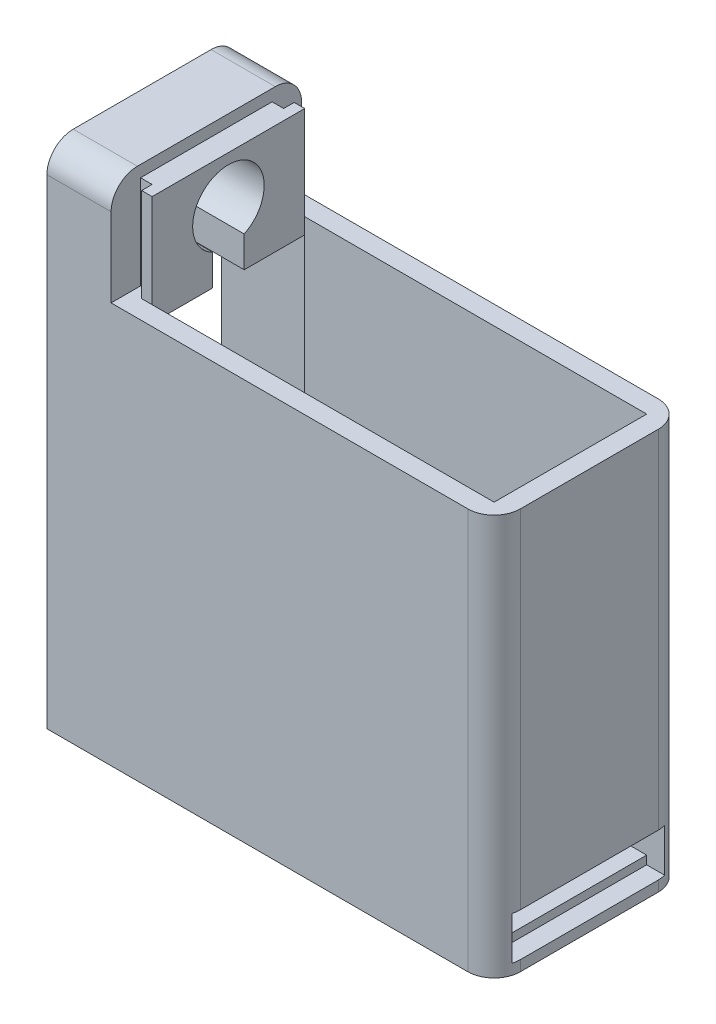
SolidWorks part; units mm, degrees
ref_plane "前视基准面" through (0, 0, 0) normal (0, 0, 1) x (1, 0, 0)
ref_plane "上视基准面" through (0, 0, 0) normal (0, 1, 0) x (1, 0, 0)
ref_plane "右视基准面" through (0, 0, 0) normal (1, 0, 0) x (0, 0, -1)
other "Configuration Table"
sketch "草图1" plane through (0, 0, 0) normal (0, 1, 0) x (1, 0, 0)
  line L1 (0, 29) -> (65, 29)
  line L2 (0, 29) -> (0, 0)
  line L3 (0, 0) -> (65, 0)
  line L4 (65, 29) -> (65, 0)
  dimension "D1" = 65
  dimension "D2" = 29
sketch "草图2" plane through (0, 0, 0) normal (0, 1, 0) x (1, 0, 0)
  line L0 (-3.6, 32.6) -> (68.6, 32.6)
  line L1 (-3.6, 32.6) -> (-3.6, -3.6)
  line L2 (-3.6, -3.6) -> (68.6, -3.6)
  line L3 (68.6, 32.6) -> (68.6, -3.6)
  dimension "D1" = 72.2
  dimension "D2" = 36.2
extrude "拉伸-薄壁1" add sketch "草图1" along normal blind 74.2 thin thin type one direction wall 3.6
extrude "凸台-拉伸2" add sketch "草图2" against normal blind 2
sketch "草图3" plane through (0, 0, 0) normal (1, 0, 0) x (0, 0, -1)
  line L1 (-0.6, 71.2) -> (29.6, 71.2)
  line L2 (-0.6, 71.2) -> (-0.6, 1)
  line L3 (-0.6, 1) -> (29.6, 1)
  line L4 (29.6, 71.2) -> (29.6, 1)
  dimension "D1" = 30.2
  dimension "D2" = 70.2
extrude "拉伸-薄壁2" add sketch "草图3" against normal blind 16.4 thin thin type one direction wall 3
sketch "草图4" plane through (0, 0, 0) normal (1, 0, 0) x (0, 0, -1)
  line L0 (-0.6, 71.2) -> (29.6, 71.2)
  line L1 (-0.6, 71.2) -> (-0.6, 1)
  line L2 (-0.6, 1) -> (29.6, 1)
  line L3 (29.6, 71.2) -> (29.6, 1)
  dimension "D1" = 30.2
  dimension "D2" = 70.2
extrude "切除-拉伸1" cut sketch "草图4" against normal blind 16.4
sketch "草图5" plane through (68.6, 0, 0) normal (1, 0, 0) x (0, 0, -1)
  line L1 (0, 0) -> (29, 0)
  line L2 (0, 0) -> (0, 4.8)
  line L3 (0, 4.8) -> (29, 4.8)
  line L4 (29, 0) -> (29, 4.8)
  dimension "D1" = 29
  dimension "D2" = 4.8
extrude "切除-拉伸2" cut sketch "草图5" against normal blind 5
sketch "草图8" plane through (-16.4, 0, 0) normal (-1, 0, 0) x (0, 0, 1)
  line L1 (-32.6, 74.2) -> (3.6, 74.2)
  line L2 (-32.6, 74.2) -> (-32.6, 94.2)
  line L3 (-32.6, 94.2) -> (3.6, 94.2)
  line L4 (3.6, 74.2) -> (3.6, 94.2)
  dimension "D1" = 20
extrude "凸台-拉伸3" add sketch "草图8" against normal blind 16.4
sketch "草图7" plane through (0, 0, 0) normal (1, 0, 0) x (0, 0, -1)
  line L1 (11.5, 88.2) -> (17.5, 88.2)
  line L2 (11.5, 88.2) -> (11.5, 71.2)
  line L3 (11.5, 71.2) -> (17.5, 71.2)
  line L4 (17.5, 88.2) -> (17.5, 71.2)
  line L5 (29, 71.2) -> (0, 71.2) construction
  dimension "D1" = 6
extrude "切除-拉伸3" cut sketch "草图7" against normal blind 17
sketch "草图9" plane through (-16.4, 0, 0) normal (-1, 0, 0) x (0, 0, 1)
  line L1 (-17.5, 71.2) -> (-11.5, 71.2)
  line L2 (-17.5, 71.2) -> (-17.5, 88.2)
  line L3 (-17.5, 88.2) -> (-11.5, 88.2)
  line L4 (-11.5, 71.2) -> (-11.5, 88.2)
extrude "凸台-拉伸4" add sketch "草图9" against normal blind 2
sketch "草图10" plane through (-16.4, 0, 0) normal (-1, 0, 0) x (0, 0, 1)
  circle A0 centre (-14.5, 83.2) radius 7.1
  dimension "D1" = 14.2
extrude "切除-拉伸4" cut sketch "草图10" against normal blind 3
sketch "草图11" plane through (0, 0, 3.6) normal (0, 0, 1) x (1, 0, 0)
  line L1 (-4.2, 94.2) -> (-2, 94.2)
  line L2 (-4.2, 94.2) -> (-4.2, 74.2)
  line L3 (-4.2, 74.2) -> (-2, 74.2)
  line L4 (-2, 94.2) -> (-2, 74.2)
extrude "切除-拉伸5" cut sketch "草图11" against normal blind 5.6
sketch "草图12" plane through (0, 0, -32.6) normal (0, 0, -1) x (-1, 0, 0)
  line L1 (2, 74.2) -> (4.2, 74.2)
  line L2 (2, 74.2) -> (2, 94.2)
  line L3 (2, 94.2) -> (4.2, 94.2)
  line L4 (4.2, 74.2) -> (4.2, 94.2)
extrude "切除-拉伸6" cut sketch "草图12" against normal blind 5.6
sketch "草图13" plane through (0, 94.2, 0) normal (0, 1, 0) x (1, 0, 0)
  line L1 (-2, 32.6) -> (0, 32.6)
  line L2 (-2, 32.6) -> (-2, 29)
  line L3 (-2, 29) -> (0, 29)
  line L4 (0, 32.6) -> (0, 29)
  line L5 (-2, -3.6) -> (0, -3.6)
  line L6 (-2, -3.6) -> (-2, 0)
  line L7 (-2, 0) -> (0, 0)
  line L8 (0, -3.6) -> (0, 0)
extrude "切除-拉伸7" cut sketch "草图13" against normal blind 20
fillet "圆角1" radius 5 1 edges at (-10.3, 94.2, 3.6)
fillet "圆角2" radius 5 1 edges at (-10.3, 94.2, -32.6)
fillet "圆角3" radius 5 2 edges at (68.6, 2.4, 0) (68.6, 36.1, 3.6)
fillet "圆角4" radius 5 2 edges at (68.6, 2.4, -29) (68.6, 36.1, -32.6)
sketch "草图14" plane through (0, 94.2, 0) normal (0, 1, 0) x (1, 0, 0)
  line L0 (-4.2, 2) -> (-4.2, -3.6) construction
  line L1 (0, 29) -> (-4.2, 29)
  line L2 (0, 29) -> (0, 0)
  line L3 (0, 0) -> (-4.2, 0)
  line L4 (-4.2, 29) -> (-4.2, 0)
extrude "切除-拉伸8" cut sketch "草图14" against normal blind 2.2
sketch "草图15" plane through (-13.4, 0, 0) normal (-1, 0, 0) x (0, 0, 1)
  circle A0 centre (-14.5, 83.2) radius 6.8
extrude "切除-拉伸9" cut sketch "草图15" against normal blind 20
sketch "草图16" plane through (-14.4, 0, 0) normal (1, 0, 0) x (0, 0, -1)
  line L1 (17.5, 71.2) -> (11.5, 71.2)
  line L2 (17.5, 71.2) -> (17.5, 76.7649)
  line L3 (17.5, 76.7649) -> (11.5, 76.7649)
  line L4 (11.5, 71.2) -> (11.5, 76.7649)
extrude "切除-拉伸10" cut sketch "草图16" against normal blind 10
sketch "草图17" plane through (0, 0, 0) normal (0, 1, 0) x (1, 0, 0)
  line L1 (0, 29) -> (65, 29)
  line L2 (0, 29) -> (0, 0)
  line L3 (0, 0) -> (65, 0)
  line L4 (65, 29) -> (65, 0)
extrude "凸台-拉伸5" add sketch "草图17" along normal blind 1.6
sketch "草图18" plane through (0, 4.8, 0) normal (0, -1, 0) x (1, 0, 0)
  line L1 (65, -29) -> (68.6, -29)
  line L2 (65, -29) -> (65, 0)
  line L3 (65, 0) -> (68.6, 0)
  line L4 (68.6, -29) -> (68.6, 0)
extrude "切除-拉伸11" cut sketch "草图18" against normal blind 3.4
sketch "草图20" plane through (65, 0, 0) normal (1, 0, 0) x (0, 0, -1)
  line L1 (3.4, 6.6) -> (25.6, 6.6)
  line L2 (3.4, 6.6) -> (3.4, 11.6)
  line L3 (3.4, 11.6) -> (25.6, 11.6)
  line L4 (25.6, 6.6) -> (25.6, 11.6)
extrude "凸台-拉伸6" add sketch "草图20" against normal blind 5.4
